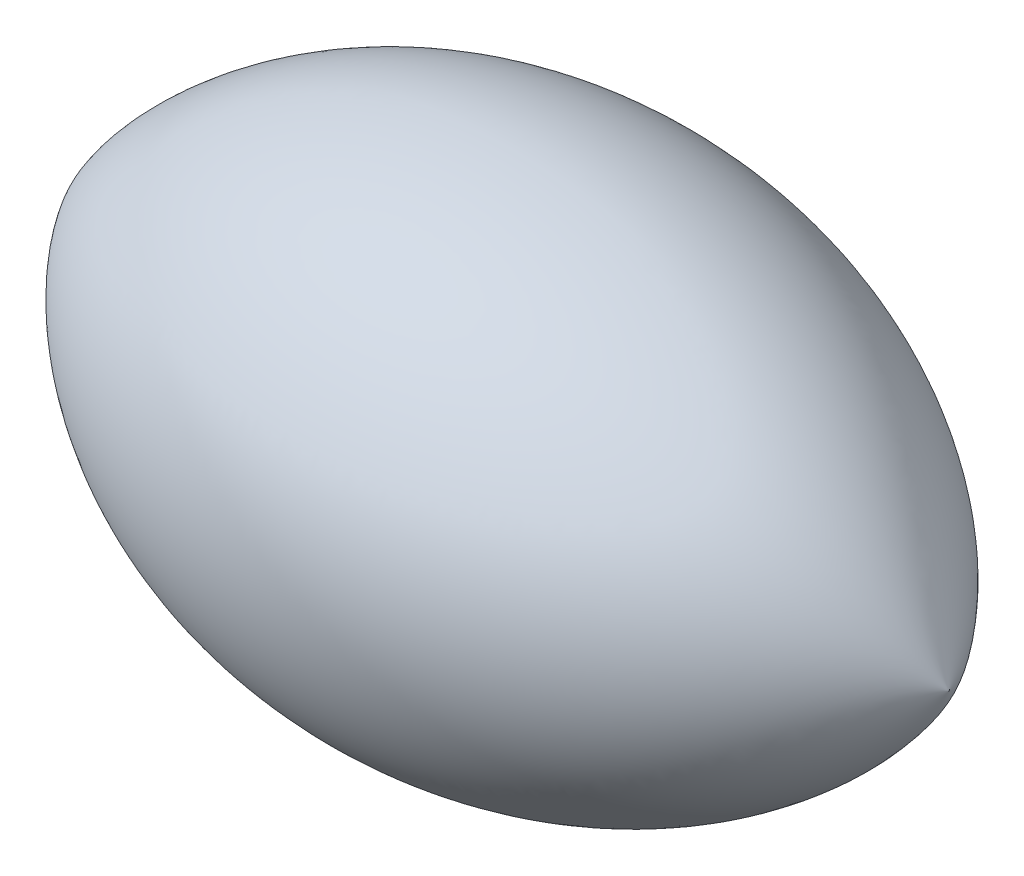
SolidWorks part; units mm, degrees
ref_plane "Front" through (0, 0, 0) normal (0, 0, 1) x (1, 0, 0)
ref_plane "Top" through (0, 0, 0) normal (0, 1, 0) x (1, 0, 0)
ref_plane "Right" through (0, 0, 0) normal (1, 0, 0) x (0, 0, -1)
sketch "Sketch1" plane through (0, 0, 0) normal (0, 0, 1) x (1, 0, 0)
  line L0 (-349.3403, 146.6027) -> (368.0527, 146.6027) construction
  line L1 (-349.3403, 146.6027) -> (368.0527, 146.6027)
  spline S0 degree 3 poles (-349.3403, 146.6027) (-206.6943, 425.1814) (224.0232, 421.1382) (368.0527, 146.6027) knots 0 0 0 0 1 1 1 1
  point P2 (-135, 285.5)
  point P4 (0, 0)
  point P6 (0, 0)
  point P7 (109.5793, 301.7137)
  point P10 (-140.2724, 297.1599)
  point P11 (-453.6145, 141.7139)
  point P12 (-355.1983, 170.8479)
  point P13 (-177.8861, 288.3309)
  point P14 (-171.5938, 327.0415)
  point P15 (-349.3403, 146.6027)
  point P16 (-110.8084, 302.7925)
  point P17 (-107.2127, 338.9415)
  point P18 (121.0058, 339.2475)
revolve "Revolve1" add sketch "Sketch1" angle 360 about L0
